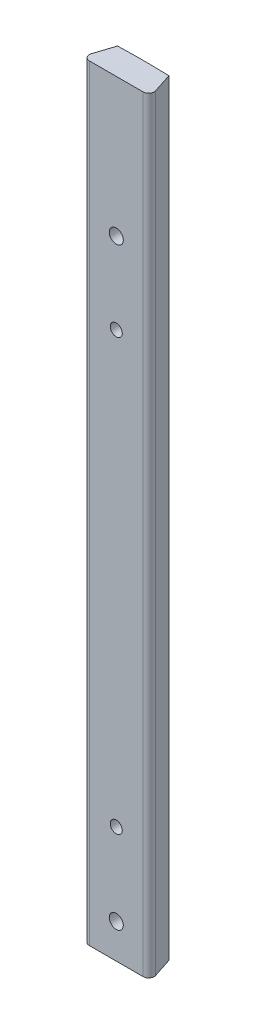
SolidWorks part; units mm, degrees
material "PLA"
ref_plane "Front Plane" through (0, 0, 0) normal (0, 0, 1) x (1, 0, 0)
ref_plane "Top Plane" through (0, 0, 0) normal (0, 1, 0) x (1, 0, 0)
ref_plane "Right Plane" through (0, 0, 0) normal (1, 0, 0) x (0, 0, -1)
sketch "Sketch2" plane through (0, 0, 0) normal (0, 1, 0) x (1, 0, 0)
  line L0 (0, -196.85) -> (0, -203.2) construction
  line L1 (5.969, -203.1123) -> (5.969, -196.9377) construction
  line L2 (-5.969, -203.1123) -> (-5.969, -196.9377) construction
  line L6 (0, -196.85) -> (0, -400.05) construction
  line L7 (8.001, -203.2) -> (-8.001, -203.2)
  line L8 (-5.969, -196.9377) -> (-8.001, -203.2)
  line L9 (5.969, -196.9377) -> (8.001, -203.2)
  arc A0 (-5.969, -203.1123) -> (5.969, -203.1123) centre (0, 0) ccw construction
  arc A1 (5.969, -196.9377) -> (-5.969, -196.9377) centre (0, -400.05) ccw
  point P1 (-5.969, -203.1123)
  point P3 (-5.969, -196.9377)
  point P8 (5.969, -196.9377)
  point P12 (0, -203.2)
  point P13 (0, -196.85)
  point P14 (5.969, -203.1123)
  point P20 (0, -203.2)
  dimension "D1" = 406.4
  dimension "D2" = 203.2
  dimension "D3" = 16.002
  dimension "D4" = 11.938
  dimension "D5" = 6.35
extrude "Boss-Extrude1" add sketch "Sketch2" along normal blind 178
ref_plane "Plane2" through (0, 0, 196.85) normal (0, 0, 1) x (1, 0, 0)
sketch "Sketch3" plane through (0, 0, 196.85) normal (0, 0, 1) x (1, 0, 0)
  line L0 (0, 0) -> (0, 146) construction
  line L1 (0, 146) -> (0, 127) construction
  line L2 (0, 146) -> (0, 8) construction
  line L3 (0, 8) -> (0, 27) construction
  circle A0 centre (0, 27) radius 1.397
  circle A1 centre (0, 127) radius 1.397
  dimension "D5" = 2.794
  dimension "D6" = 2.794
  dimension "D1" = 146
  dimension "D2" = 19
  dimension "D3" = 138
  dimension "D4" = 19
hole_wizard "CBORE for #4 Binding Head Machine Screw3" positions "3DSketch5" profile "Sketch8" counterbore size "#4" standard "ANSI Inch" end condition through all
sketch3d "3DSketch5"
  line L0 (0, 0, 196.85) -> (0, 146, 196.85) construction
  point P0 (0, 8, 196.85)
  point P3 (0, 145.8754, 196.85)
sketch "Sketch8" plane through (0, 8, 196.85) normal (1, 0, 0) x (0, 1, 0)
  line L0 (0, 0) -> (0, 6.35)
  line L1 (0, 6.35) -> (1.6319, 6.35)
  line L3 (1.6319, 6.35) -> (1.6319, 1.7272)
  line L4 (1.6319, 1.7272) -> (3.3731, 1.7272)
  line L5 (3.3731, 1.7272) -> (3.3731, 0)
  line L7 (3.3731, 0) -> (0, 0)
  line L11 (0, -6.35) -> (0, 107.95) construction
  dimension "Thru Hole Dia." = 3.2639
  dimension "Thru Hole Depth" = 6.35
  dimension "C'Bore Dia." = 6.7462
  dimension "C'Bore Depth" = 1.7272
extrude "Cut-Extrude1" cut sketch "Sketch3" along normal through all
fillet "Fillet1" radius 1.27 2 edges at (8.001, 89, 203.2) (-8.001, 89, 203.2)
